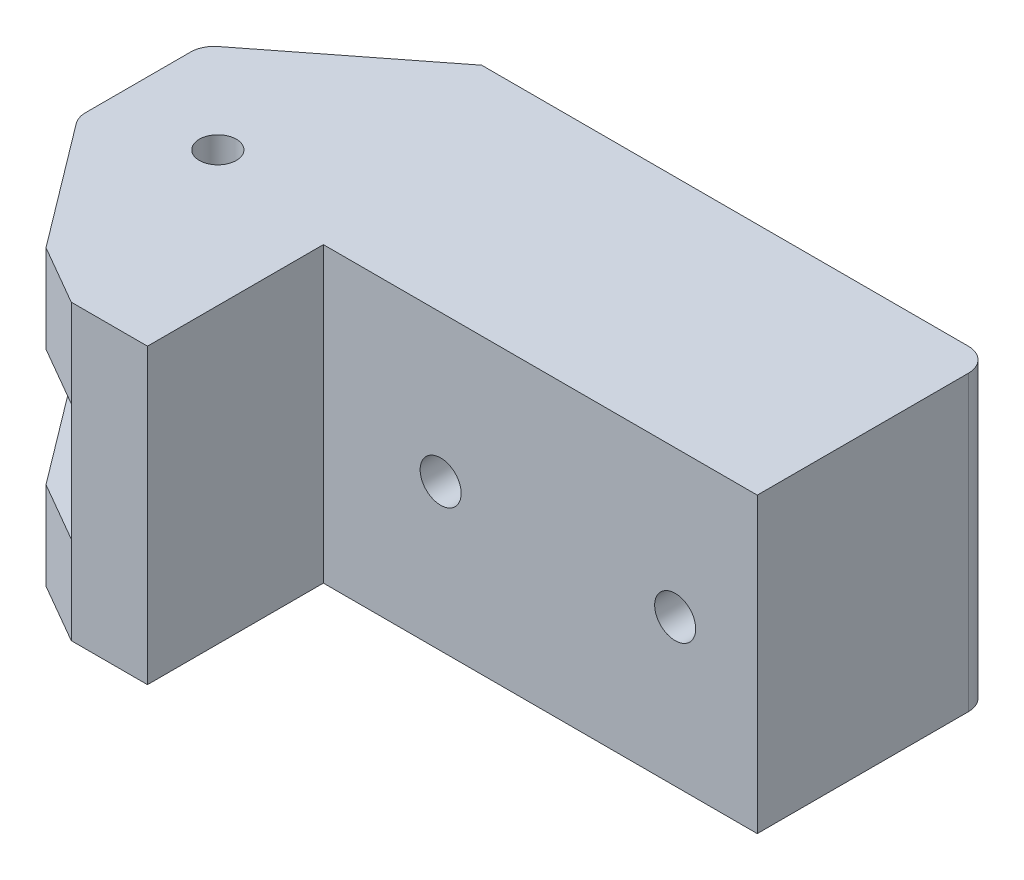
SolidWorks part; units mm, degrees
ref_plane "Front Plane" through (0, 0, 0) normal (0, 0, 1) x (1, 0, 0)
ref_plane "Top Plane" through (0, 0, 0) normal (0, 1, 0) x (1, 0, 0)
ref_plane "Right Plane" through (0, 0, 0) normal (1, 0, 0) x (0, 0, -1)
sketch "Sketch1" plane through (0, 0, 0) normal (0, 1, 0) x (1, 0, 0)
  line L0 (0, 0) -> (-43.5, 0)
  line L1 (-43.5, 0) -> (-43.5, -35) construction
  line L2 (-43.5, -35) -> (-37, -35)
  line L3 (-37, -35) -> (-37, -20)
  line L4 (-37, -20) -> (0, -20)
  line L5 (0, -20) -> (0, 0)
  line L6 (-43.5, 0) -> (-56.8853, -10.4577)
  line L7 (-56.8853, -10.4577) -> (-56.8853, -21.0577)
  line L8 (-56.8853, -21.0577) -> (-48.5962, -32.0577)
  line L9 (-48.5962, -32.0577) -> (-43.5, -35)
  line L10 (-43.5, -17.5) -> (-48.5, -17.5) construction
  circle A0 centre (-48.5, -17.5) radius 1.575
  dimension "D11" = 3.15
  dimension "D1" = 43.5
  dimension "D2" = 35
  dimension "D3" = 20
  dimension "D4" = 37
  dimension "D5" = 30
  dimension "D6" = 38
  dimension "D7" = 10.6
  dimension "D8" = 37
  dimension "D9" = 11
  dimension "D10" = 5
extrude "Boss-Extrude1" add sketch "Sketch1" along normal mid plane 25
sketch "Sketch2" plane through (0, 0, 35) normal (0, 0, 1) x (1, 0, 0)
  line L0 (-43.5, 12.5) -> (-43.5, -12.5) construction
  line L1 (-43.5, -5) -> (-56.8853, -5)
  line L2 (-43.5, -5) -> (-43.5, 5)
  line L3 (-43.5, 5) -> (-56.8853, 5)
  line L4 (-56.8853, -5) -> (-56.8853, 5)
  line L5 (-56.8853, 12.5) -> (-56.8853, -12.5) construction
  line L6 (-56.8853, 12.5) -> (-48.5962, 12.5) construction
  dimension "D1" = 7.5
  dimension "D2" = 10
extrude "Cut-Extrude1" cut sketch "Sketch2" against normal through all
sketch "Sketch3" plane through (0, 0, 20) normal (0, 0, 1) x (1, 0, 0)
  line L1 (0, 0) -> (-27, 0) construction
  line L2 (-37, 12.5) -> (-37, -12.5) construction
  circle A0 centre (-27, 0) radius 1.75
  circle A1 centre (-7, 0) radius 1.75
  dimension "D1" = 3.5
  dimension "D2" = 20
  dimension "D3" = 10
extrude "Cut-Extrude2" cut sketch "Sketch3" against normal blind 25
sketch "Sketch4" plane through (0, 0, 0) normal (0, 0, -1) x (-1, 0, 0)
  circle A0 centre (7, 0) radius 4
  circle A2 centre (27, 0) radius 4
extrude "Cut-Extrude3" cut sketch "Sketch4" against normal blind 4
fillet "Fillet1" radius 2 5 edges at (0, 0, 0) (-56.8853, 8.75, 10.4577) (-56.8853, 8.75, 21.0577) (-56.8853, -8.75, 21.0577) (-56.8853, -8.75, 10.4577)
